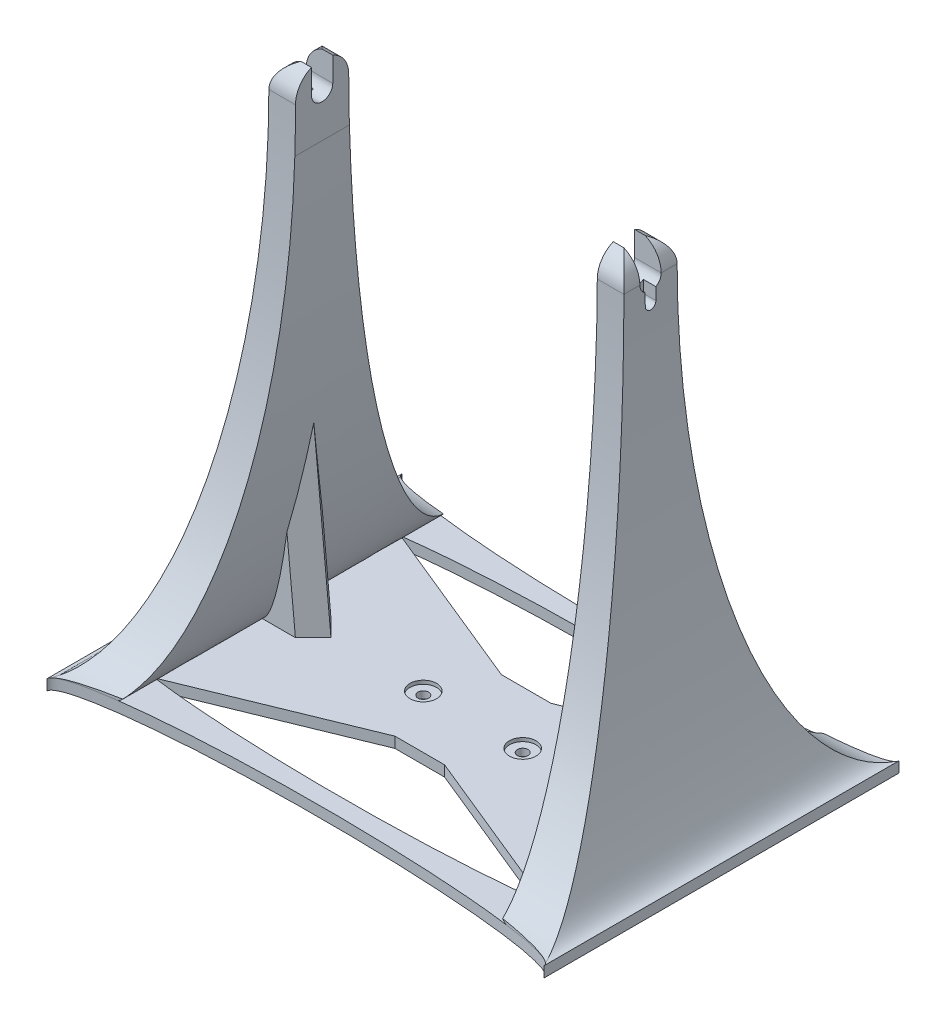
SolidWorks part; units mm, degrees
ref_plane "Front Plane" through (0, 0, 0) normal (0, 0, 1) x (1, 0, 0)
ref_plane "Top Plane" through (0, 0, 0) normal (0, 1, 0) x (1, 0, 0)
ref_plane "Right Plane" through (0, 0, 0) normal (1, 0, 0) x (0, 0, -1)
sketch "Sketch1" plane through (0, 0, 0) normal (0, 1, 0) x (1, 0, 0)
  line L0 (0, 57.5) -> (0, 42.5) construction
  line L1 (-14, 0) -> (-7, 15) construction
  line L2 (-7, 15) -> (-55, 34.6394)
  line L3 (-70, 30) -> (-70, 50) construction
  line L4 (-70, 50) -> (0, 50) construction
  line L5 (0, 0) -> (-47.9407, 0) construction
  line L6 (-70, 50) -> (-70, -50)
  line L7 (0, 42.5) -> (0, 37.5) construction
  line L8 (-7, 15) -> (0, 0) construction
  line L9 (-7, 15) -> (7, 15)
  line L10 (70, 30) -> (70, 50) construction
  line L11 (0, 22.5) -> (0, 37.5) construction
  line L12 (-70, 30) -> (0, 30) construction
  line L13 (14, 0) -> (7, 15) construction
  line L14 (70, 50) -> (70, -50)
  line L15 (7, 15) -> (55, 34.6394)
  line L16 (14, 0) -> (7, -15) construction
  line L17 (-70, -30) -> (0, -30) construction
  line L18 (0, -22.5) -> (0, -37.5) construction
  line L19 (70, -30) -> (70, -50) construction
  line L20 (-7, -15) -> (0, 0) construction
  line L21 (0, -42.5) -> (0, -37.5) construction
  line L22 (-70, -50) -> (0, -50) construction
  line L23 (-70, -30) -> (-70, -50) construction
  line L24 (-14, 0) -> (-7, -15) construction
  line L25 (0, -57.5) -> (0, -42.5) construction
  line L26 (7, -15) -> (55, -34.6394)
  line L27 (-7, -15) -> (7, -15)
  line L28 (-7, -15) -> (-55, -34.6394)
  ellipse E0 centre (0, 50) end of major axis (70, 50) minor radius 7.5 (-70, 50) -> (70, 50) ccw
  ellipse E1 centre (0, 30) end of major axis (-70, 30) minor radius 7.5 (55, 34.6394) -> (-55, 34.6394) ccw
  ellipse E2 centre (0, -30) end of major axis (-70, -30) minor radius 7.5 (55, -34.6394) -> (-55, -34.6394) cw
  ellipse E3 centre (0, -50) end of major axis (70, -50) minor radius 7.5 (-70, -50) -> (70, -50) cw
  point P0 (0, 40)
  point P12 (97.9451, 0)
  point P29 (0, 15)
  point P32 (-70, 0)
  point P57 (70, 0)
  line B0 (-14, 0) -> (0, 0) construction
  line B1 (0, 0) -> (14, 0) construction
  circle B2 centre (14, 0) radius 1.5
  circle B3 centre (-14, 0) radius 1.5
  line B4 (14, 0) -> (0, 0) construction
  line B5 (0, 0) -> (-14, 0) construction
  circle B6 centre (-14, 0) radius 1.5
  circle B7 centre (14, 0) radius 1.5
  dimension "D3" = 25
  dimension "D1" = 5
  dimension "D2" = 20
  dimension "D4" = 50
  dimension "D5" = 15
  dimension "D6" = 15
  dimension "D7" = 70
sketch_block_instance "Block1-1"
sketch_block "Block1"
sketch_block_instance "Block1-5"
extrude "Boss-Extrude1" add sketch "Sketch1" along normal blind 3 contours E0 E1 L9 L2 region at (0, 0, 0)
sketch "Sketch2" plane through (0, 3, 0) normal (0, 1, 0) x (1, 0, 0)
  circle A0 centre (-14, 0) radius 3.75
  circle A1 centre (14, 0) radius 3.75
  dimension "D1" = 7.5
extrude "Cut-Extrude1" cut sketch "Sketch2" against normal blind 1
sketch "Sketch3" plane through (0, 0, 0) normal (0, 0, 1) x (1, 0, 0)
  line L0 (-50, 135.5) -> (-90, 135.5) construction
  line L1 (-42.5, 143) -> (-42.5, 123)
  line L2 (-67.5, 123) -> (-42.5, 123) construction
  line L3 (70, 3) -> (-70, 3) construction
  line L4 (0, 0) -> (0, 59.5964) construction
  line L5 (-70, 3) -> (-55, 3)
  line L6 (-55, 123) -> (-55, 3) construction
  line L7 (55, 123) -> (55, 3) construction
  line L8 (67.5, 123) -> (42.5, 123) construction
  line L9 (70, 3) -> (55, 3)
  line L10 (42.5, 143) -> (42.5, 123)
  line L11 (-70, 3) -> (-70, 0) construction
  arc A0 (-42.5244, 128) -> (-42.5, 128) centre (-42.5, 135.5) ccw
  arc A1 (-42.5, 143) -> (-50, 135.5) centre (-42.5, 135.5) ccw
  arc A2 (42.5, 143) -> (50, 135.5) centre (42.5, 135.5) cw
  arc A3 (42.5244, 128) -> (42.5, 128) centre (42.5, 135.5) cw
  ellipse E0 centre (55, 123) end of major axis (55, 243) minor radius 12.5 (55, 3) -> (42.5, 123) cw
  ellipse E1 centre (-70, 135.5) end of major axis (-70, 268) minor radius 20 (-70, 3) -> (-50, 135.5) ccw
  ellipse E2 centre (-55, 123) end of major axis (-55, 243) minor radius 12.5 (-55, 3) -> (-42.5, 123) ccw
  ellipse E3 centre (70, 135.5) end of major axis (70, 268) minor radius 20 (70, 3) -> (50, 135.5) cw
  point P10 (-70, 1.5)
  dimension "D5" = 15
  dimension "D1" = 42.5
  dimension "D2" = 20
  dimension "D3" = 140
  dimension "D4" = 15
  dimension "D6" = 85
  dimension "D7" = 7.5
  dimension "D8" = 20
extrude "Boss-Extrude2" add sketch "Sketch3" along normal blind 50 and the other way blind 50 contours L5 E2 L1 A1 E1 | L9 E3 A2 L10 E0 region at (-50.108, 65.2961, 0) region at (50.108, 65.2961, 0)
sketch "Sketch4" plane through (0, 0, 0) normal (1, 0, 0) x (0, 0, -1)
  line L0 (0, 0) -> (0, -6.4833) construction
  line L1 (-50, 3) -> (-50, 143)
  line L2 (-50, 143) -> (50, 143)
  line L3 (50, 3) -> (50, 143)
  line L4 (-3, 135.5) -> (-3, 142.3739)
  line L5 (50, 135.5) -> (-50, 135.5) construction
  line L7 (3, 135.5) -> (3, 142.3739)
  arc A0 (7.5, 135.5) -> (3, 142.3739) centre (0, 135.5) ccw
  arc A1 (-3, 135.5) -> (3, 135.5) centre (0, 135.5) ccw
  arc A2 (-3, 142.3739) -> (-7.5, 135.5) centre (0, 135.5) ccw
  ellipse E0 centre (-50, 135.5) end of major axis (-50, 268) minor radius 42.5 (-50, 3) -> (-7.5, 135.5) ccw
  ellipse E1 centre (50, 135.5) end of major axis (50, 268) minor radius 42.5 (50, 3) -> (7.5, 135.5) cw
  point P25 (0, 143)
  dimension "D1" = 15
  dimension "D2" = 6
extrude "Cut-Extrude2" cut sketch "Sketch4" against normal blind 100 and the other way blind 100 contours L1 E0 A0 L2 | E1 L3 L2 A0 | A1 L7 A0 E1 L3 L2 L1 E0 A2 L4 region at (0, 73, 48.2795)
sketch "Sketch5" plane through (0, 0, 0) normal (0, -1, 0) x (1, 0, 0)
  line L0 (-70, 50) -> (-55, 50) construction
  ellipse E0 centre (0, 50) end of major axis (-70, 50) minor radius 7.5
  ellipse E1 centre (0, 50) end of major axis (70, 50) minor radius 7.5 (-70, 50) -> (70, 50) ccw construction
  ellipse E2 centre (0, -50) end of major axis (-70, -50) minor radius 7.5
extrude "Cut-Extrude3" cut sketch "Sketch5" against normal blind 50
sketch "Sketch7" plane through (0, 0, 0) normal (0, 0, 1) x (1, 0, 0)
  line L0 (-62.5, 3) -> (-44.8471, 53)
  line L1 (-70, 3) -> (-55, 3) construction
  line L2 (-44.8471, 53) -> (-40, 3)
  line L3 (55, 3) -> (-55, 3) construction
  line L4 (-40, 3) -> (-62.5, 3)
  line L5 (-40, 147.3739) -> (40, 147.3739) construction
  line L6 (-40, 226.9739) -> (40, 226.9739) construction
  line L7 (-40, 226.9739) -> (-40, 16.9739) construction
  line L8 (-40, 16.9739) -> (40, 16.9739) construction
  line L9 (40, 226.9739) -> (40, 16.9739) construction
  line L10 (-40, 96.5739) -> (40, 121.9739) construction
  line L11 (-40, 96.5739) -> (40, 96.5739) construction
  line L12 (40, 121.9739) -> (-40, 147.3739) construction
  line L13 (-42.5, 135.5) -> (-40, 135.5) construction
  line L14 (0, 0) -> (0, -33.258) construction
  line L15 (40, 3) -> (62.5, 3)
  line L16 (42.5, 135.5) -> (40, 135.5) construction
  line L17 (44.8471, 53) -> (40, 3)
  line L18 (62.5, 3) -> (44.8471, 53)
  ellipse E0 centre (-55, 123) end of major axis (-55, 243) minor radius 12.5 (-53.5057, 3.8605) -> (-42.5, 123) ccw construction
  point P29 (-51.25, 3)
  point P36 (0, 0)
  point P37 (42.5, 135.5)
  dimension "D1" = 210
  dimension "D2" = 80
  dimension "D3" = 50.8
  dimension "D4" = 50
  dimension "D5" = 5
  dimension "D6" = 22.5
extrude "Boss-Extrude3" add sketch "Sketch7" along normal blind 5 and the other way blind 5
chamfer "Chamfer1" distance 5 angle 45 4 edges at (42.4235, 28, -5) (42.4235, 28, 5) (-42.4235, 28, -5) (-42.4235, 28, 5)
sketch "Sketch9" plane through (70, 0, 0) normal (1, 0, 0) x (0, 0, -1)
  line L0 (0, 139.9792) -> (0, 135.3826) construction
  line L1 (-1.5, 129.5) -> (-1.5, 142.3739)
  line L2 (-1.5, 142.3739) -> (1.5, 142.3739)
  line L3 (1.5, 142.3739) -> (1.5, 129.5)
  arc A0 (-1.5, 129.5) -> (1.5, 129.5) centre (0, 129.5) ccw
  arc A3 (-3, 135.5) -> (3, 135.5) centre (0, 135.5) ccw construction
  point P1 (0, 0)
  point P2 (0, 129.3631)
  dimension "D1" = 3
  dimension "D2" = 6
extrude "Cut-Extrude4" cut sketch "Sketch9" against normal blind 23.5
sketch "Sketch10" plane through (-70, 0, 0) normal (-1, 0, 0) x (0, 0, 1)
  line L0 (1.5, 129.5) -> (1.5, 142.3739)
  line L1 (1.5, 142.3739) -> (-1.5, 142.3739)
  line L2 (-1.5, 142.3739) -> (-1.5, 129.5)
  arc A0 (-1.5, 129.5) -> (1.5, 129.5) centre (0, 129.5) ccw
  arc A1 (-1.5, 129.5) -> (1.5, 129.5) centre (0, 129.5) ccw construction
extrude "Cut-Extrude5" cut sketch "Sketch10" against normal blind 23.5
